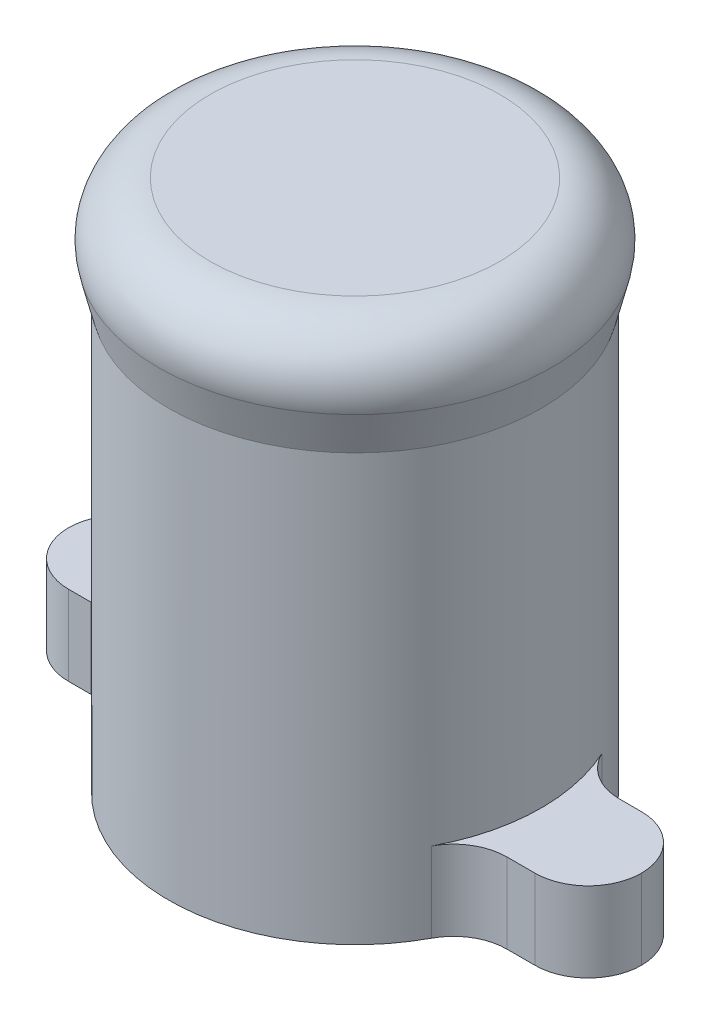
SolidWorks part; units mm, degrees
ref_plane "Front Plane" through (0, 0, 0) normal (0, 0, 1) x (1, 0, 0)
ref_plane "Top Plane" through (0, 0, 0) normal (0, 1, 0) x (1, 0, 0)
ref_plane "Right Plane" through (0, 0, 0) normal (1, 0, 0) x (0, 0, -1)
sketch "Sketch1" plane through (0, 0, 0) normal (0, 0, 1) x (1, 0, 0)
  line L0 (0, 0) -> (0, 10)
  line L1 (0, 10) -> (4, 10)
  line L5 (3.5, 0) -> (0, 0)
  line L8 (3.5, 0) -> (3.5, 8)
  line L9 (3.5, 8) -> (4, 10)
  dimension "D1" = 4
  dimension "D2" = 10
  dimension "D3" = 3.5
  dimension "D4" = 8
revolve "Revolve1" add sketch "Sketch1" angle 360 about L0
sketch "Sketch3" plane through (0, 0, 0) normal (0, -1, 0) x (1, 0, 0)
  line L1 (-1.5, -1.5) -> (1.5, -1.5)
  line L2 (-1.5, -1.5) -> (-1.5, 1.5)
  line L3 (-1.5, 1.5) -> (1.5, 1.5)
  line L4 (1.5, -1.5) -> (1.5, 1.5)
  line L5 (-1.5, -1.5) -> (1.5, 1.5) construction
  line L6 (-1.5, 1.5) -> (1.5, -1.5) construction
  point P0 (0, 0)
  dimension "D1" = 3
  dimension "D2" = 3
extrude "Cut-Extrude2" cut sketch "Sketch3" against normal blind 3.5 draft 3
sketch "Sketch4" plane through (0, 0, 0) normal (0, 1, 0) x (1, 0, 0)
  line L0 (-3.5, 0.119) -> (0, 0) construction
  line L1 (-1.5, 1.119) -> (-5.5, 1.119)
  line L2 (-1.5, 1.119) -> (-1.5, -0.881)
  line L3 (-1.5, -0.881) -> (-5.5, -0.881)
  line L4 (-5.5, 1.119) -> (-5.5, -0.881)
  line L5 (-1.5, 1.119) -> (-5.5, -0.881) construction
  line L6 (-1.5, -0.881) -> (-5.5, 1.119) construction
  line L7 (5.5, -1.119) -> (1.5, -1.119)
  line L8 (5.5, -1.119) -> (5.5, 0.881)
  line L9 (5.5, 0.881) -> (1.5, 0.881)
  line L10 (1.5, -1.119) -> (1.5, 0.881)
  line L11 (5.5, -1.119) -> (1.5, 0.881) construction
  line L12 (5.5, 0.881) -> (1.5, -1.119) construction
  line L13 (0, 0) -> (3.5, -0.119) construction
  line L14 (-1.5, -1.5) -> (-1.5, 1.5) construction
  line L15 (-3.5, 3.4123) -> (-3.5, -3.7854) construction
  circle A0 centre (0, 0) radius 3.5 construction
  point P0 (-3.5, 0.119)
  point P6 (3.5, -0.119)
  dimension "D1" = 2
  dimension "D2" = 2
extrude "Boss-Extrude1" add sketch "Sketch4" along normal blind 1.5
fillet "Fillet1" radius 1 9 edges at (3.3163, 0.75, 1.119) (5.5, 0.75, 1.119) (5.5, 0.75, -0.881) (3.3873, 0.75, -0.881) (-3.3163, 0.75, -1.119) (-5.5, 0.75, -1.119) (-5.5, 0.75, 0.881) (-3.3873, 0.75, 0.881) (0, 10, -4)
